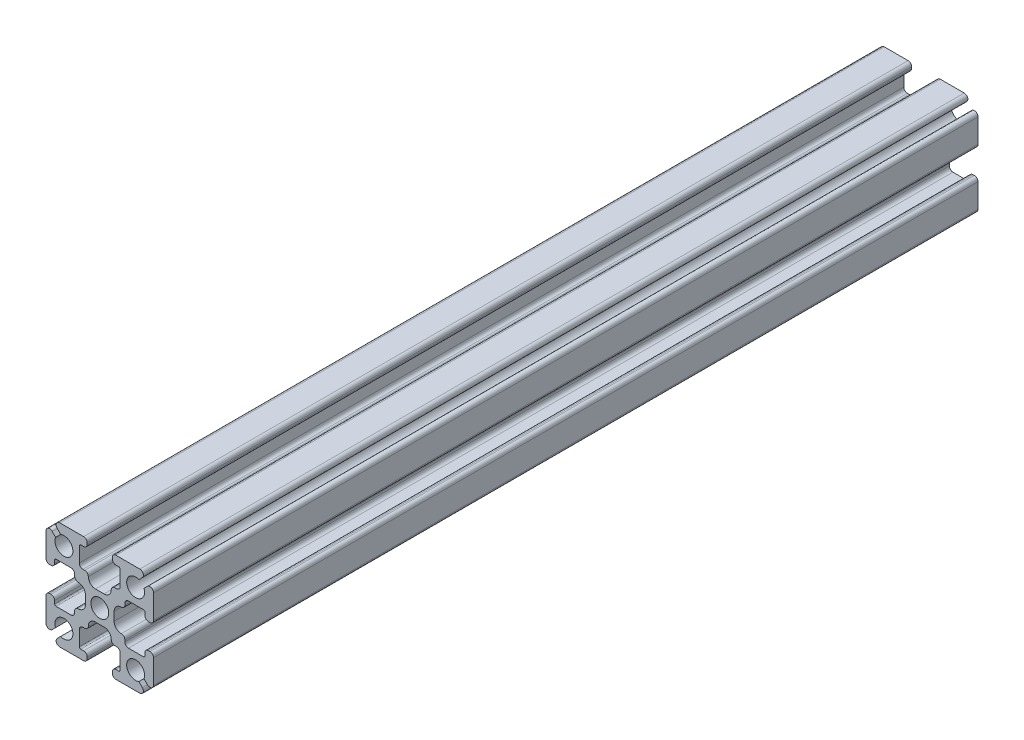
SolidWorks part; units mm, degrees
ref_plane "Front" through (0, 0, 0) normal (0, 0, 1) x (1, 0, 0)
ref_plane "Top" through (0, 0, 0) normal (0, 1, 0) x (1, 0, 0)
ref_plane "Right" through (0, 0, 0) normal (1, 0, 0) x (0, 0, -1)
sketch "Sketch1" plane through (0, 0, 0) normal (0, 0, 1) x (1, 0, 0)
  line L0 (6.6464, 5.9393) -> (6.1636, 5.4565)
  line L1 (5.4565, 6.1636) -> (5.9393, 6.6464)
  line L2 (5.5858, 7.5) -> (2.25, 7.5)
  line L3 (1.75, 7) -> (1.75, 6.8)
  line L4 (2.25, 6.3) -> (2.65, 6.3)
  line L5 (2.85, 6.1) -> (2.85, 4)
  line L6 (2.35, 3.5) -> (2.1, 3.5)
  line L7 (0.6, 2) -> (-0.6, 2)
  line L8 (-2.1, 3.5) -> (-2.35, 3.5)
  line L9 (-2.85, 4) -> (-2.85, 6.1)
  line L10 (-2.65, 6.3) -> (-2.25, 6.3)
  line L11 (-1.75, 6.8) -> (-1.75, 7)
  line L12 (-2.25, 7.5) -> (-5.5858, 7.5)
  line L13 (-5.9393, 6.6464) -> (-5.4565, 6.1636)
  line L14 (-6.1636, 5.4565) -> (-6.6464, 5.9393)
  line L15 (-7.5, 5.5858) -> (-7.5, 2.25)
  line L16 (-7, 1.75) -> (-6.8, 1.75)
  line L17 (-6.3, 2.25) -> (-6.3, 2.65)
  line L18 (-6.1, 2.85) -> (-4, 2.85)
  line L19 (-3.5, 2.35) -> (-3.5, 2.1)
  line L20 (-2, 0.6) -> (-2, -0.6)
  line L21 (-3.5, -2.1) -> (-3.5, -2.35)
  line L22 (-4, -2.85) -> (-6.1, -2.85)
  line L23 (-6.3, -2.65) -> (-6.3, -2.25)
  line L24 (-6.8, -1.75) -> (-7, -1.75)
  line L25 (-7.5, -2.25) -> (-7.5, -5.5858)
  line L26 (-6.6464, -5.9393) -> (-6.1636, -5.4565)
  line L27 (-5.4565, -6.1636) -> (-5.9393, -6.6464)
  line L28 (-5.5858, -7.5) -> (-2.25, -7.5)
  line L29 (-1.75, -7) -> (-1.75, -6.8)
  line L30 (-2.25, -6.3) -> (-2.65, -6.3)
  line L31 (-2.85, -6.1) -> (-2.85, -4)
  line L32 (-2.35, -3.5) -> (-2.1, -3.5)
  line L33 (-0.6, -2) -> (0.6, -2)
  line L34 (2.1, -3.5) -> (2.35, -3.5)
  line L35 (2.85, -4) -> (2.85, -6.1)
  line L36 (2.65, -6.3) -> (2.25, -6.3)
  line L37 (1.75, -6.8) -> (1.75, -7)
  line L38 (2.25, -7.5) -> (5.5858, -7.5)
  line L39 (5.9393, -6.6464) -> (5.4565, -6.1636)
  line L40 (6.1636, -5.4565) -> (6.6464, -5.9393)
  line L41 (7.5, -5.5858) -> (7.5, -2.25)
  line L42 (7, -1.75) -> (6.8, -1.75)
  line L43 (6.3, -2.25) -> (6.3, -2.65)
  line L44 (6.1, -2.85) -> (4, -2.85)
  line L45 (3.5, -2.35) -> (3.5, -2.1)
  line L46 (2, -0.6) -> (2, 0.6)
  line L47 (3.5, 2.1) -> (3.5, 2.35)
  line L48 (4, 2.85) -> (6.1, 2.85)
  line L49 (6.3, 2.65) -> (6.3, 2.25)
  line L50 (6.8, 1.75) -> (7, 1.75)
  line L51 (7.5, 2.25) -> (7.5, 5.5858)
  circle A0 centre (0, 0) radius 1.25
  arc A1 (6.1636, 5.4565) -> (5.4565, 6.1636) centre (5, 5) cw
  arc A2 (5.9393, 6.6464) -> (5.5858, 7.5) centre (5.5858, 7) ccw
  arc A3 (2.25, 7.5) -> (1.75, 7) centre (2.25, 7) ccw
  arc A4 (1.75, 6.8) -> (2.25, 6.3) centre (2.25, 6.8) ccw
  arc A5 (2.65, 6.3) -> (2.85, 6.1) centre (2.65, 6.1) cw
  arc A6 (2.85, 4) -> (2.35, 3.5) centre (2.35, 4) cw
  arc A7 (2.1, 3.5) -> (1.6, 3) centre (2.1, 3) ccw
  arc A8 (1.6, 3) -> (0.6, 2) centre (0.6, 3) cw
  arc A9 (-0.6, 2) -> (-1.6, 3) centre (-0.6, 3) cw
  arc A10 (-1.6, 3) -> (-2.1, 3.5) centre (-2.1, 3) ccw
  arc A11 (-2.35, 3.5) -> (-2.85, 4) centre (-2.35, 4) cw
  arc A12 (-2.85, 6.1) -> (-2.65, 6.3) centre (-2.65, 6.1) cw
  arc A13 (-2.25, 6.3) -> (-1.75, 6.8) centre (-2.25, 6.8) ccw
  arc A14 (-1.75, 7) -> (-2.25, 7.5) centre (-2.25, 7) ccw
  arc A15 (-5.5858, 7.5) -> (-5.9393, 6.6464) centre (-5.5858, 7) ccw
  arc A16 (-5.4565, 6.1636) -> (-6.1636, 5.4565) centre (-5, 5) cw
  arc A17 (-6.6464, 5.9393) -> (-7.5, 5.5858) centre (-7, 5.5858) ccw
  arc A18 (-7.5, 2.25) -> (-7, 1.75) centre (-7, 2.25) ccw
  arc A19 (-6.8, 1.75) -> (-6.3, 2.25) centre (-6.8, 2.25) ccw
  arc A20 (-6.3, 2.65) -> (-6.1, 2.85) centre (-6.1, 2.65) cw
  arc A21 (-4, 2.85) -> (-3.5, 2.35) centre (-4, 2.35) cw
  arc A22 (-3.5, 2.1) -> (-3, 1.6) centre (-3, 2.1) ccw
  arc A23 (-3, 1.6) -> (-2, 0.6) centre (-3, 0.6) cw
  arc A24 (-2, -0.6) -> (-3, -1.6) centre (-3, -0.6) cw
  arc A25 (-3, -1.6) -> (-3.5, -2.1) centre (-3, -2.1) ccw
  arc A26 (-3.5, -2.35) -> (-4, -2.85) centre (-4, -2.35) cw
  arc A27 (-6.1, -2.85) -> (-6.3, -2.65) centre (-6.1, -2.65) cw
  arc A28 (-6.3, -2.25) -> (-6.8, -1.75) centre (-6.8, -2.25) ccw
  arc A29 (-7, -1.75) -> (-7.5, -2.25) centre (-7, -2.25) ccw
  arc A30 (-7.5, -5.5858) -> (-6.6464, -5.9393) centre (-7, -5.5858) ccw
  arc A31 (-6.1636, -5.4565) -> (-5.4565, -6.1636) centre (-5, -5) cw
  arc A32 (-5.9393, -6.6464) -> (-5.5858, -7.5) centre (-5.5858, -7) ccw
  arc A33 (-2.25, -7.5) -> (-1.75, -7) centre (-2.25, -7) ccw
  arc A34 (-1.75, -6.8) -> (-2.25, -6.3) centre (-2.25, -6.8) ccw
  arc A35 (-2.65, -6.3) -> (-2.85, -6.1) centre (-2.65, -6.1) cw
  arc A36 (-2.85, -4) -> (-2.35, -3.5) centre (-2.35, -4) cw
  arc A37 (-2.1, -3.5) -> (-1.6, -3) centre (-2.1, -3) ccw
  arc A38 (-1.6, -3) -> (-0.6, -2) centre (-0.6, -3) cw
  arc A39 (0.6, -2) -> (1.6, -3) centre (0.6, -3) cw
  arc A40 (1.6, -3) -> (2.1, -3.5) centre (2.1, -3) ccw
  arc A41 (2.35, -3.5) -> (2.85, -4) centre (2.35, -4) cw
  arc A42 (2.85, -6.1) -> (2.65, -6.3) centre (2.65, -6.1) cw
  arc A43 (2.25, -6.3) -> (1.75, -6.8) centre (2.25, -6.8) ccw
  arc A44 (1.75, -7) -> (2.25, -7.5) centre (2.25, -7) ccw
  arc A45 (5.5858, -7.5) -> (5.9393, -6.6464) centre (5.5858, -7) ccw
  arc A46 (5.4565, -6.1636) -> (6.1636, -5.4565) centre (5, -5) cw
  arc A47 (6.6464, -5.9393) -> (7.5, -5.5858) centre (7, -5.5858) ccw
  arc A48 (7.5, -2.25) -> (7, -1.75) centre (7, -2.25) ccw
  arc A49 (6.8, -1.75) -> (6.3, -2.25) centre (6.8, -2.25) ccw
  arc A50 (6.3, -2.65) -> (6.1, -2.85) centre (6.1, -2.65) cw
  arc A51 (4, -2.85) -> (3.5, -2.35) centre (4, -2.35) cw
  arc A52 (3.5, -2.1) -> (3, -1.6) centre (3, -2.1) ccw
  arc A53 (3, -1.6) -> (2, -0.6) centre (3, -0.6) cw
  arc A54 (2, 0.6) -> (3, 1.6) centre (3, 0.6) cw
  arc A55 (3, 1.6) -> (3.5, 2.1) centre (3, 2.1) ccw
  arc A56 (3.5, 2.35) -> (4, 2.85) centre (4, 2.35) cw
  arc A57 (6.1, 2.85) -> (6.3, 2.65) centre (6.1, 2.65) cw
  arc A58 (6.3, 2.25) -> (6.8, 1.75) centre (6.8, 2.25) ccw
  arc A59 (7, 1.75) -> (7.5, 2.25) centre (7, 2.25) ccw
  arc A60 (7.5, 5.5858) -> (6.6464, 5.9393) centre (7, 5.5858) ccw
extrude "Boss-Extrude1" add sketch "Sketch1" along normal blind 115
